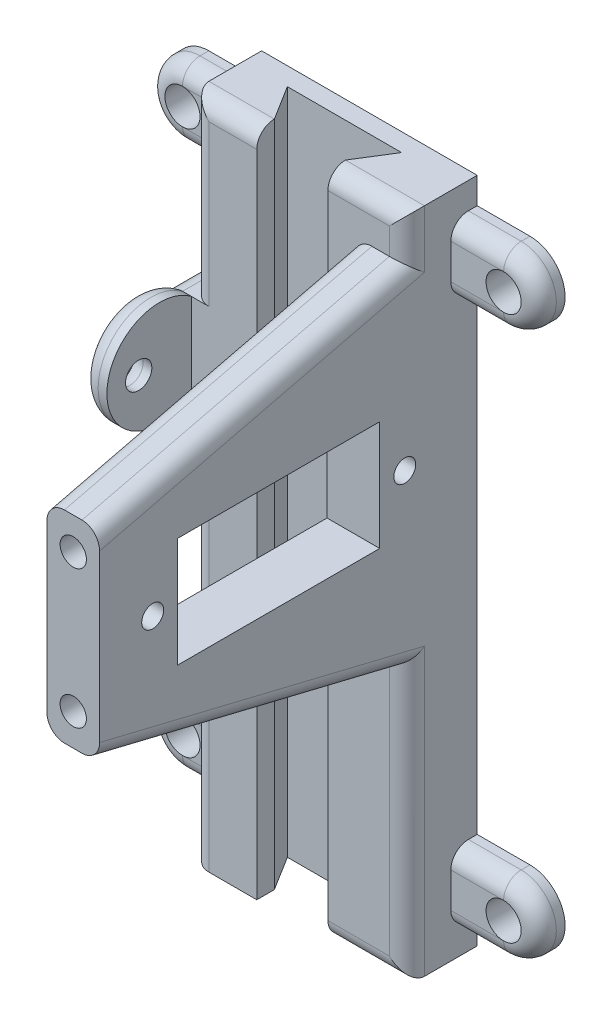
SolidWorks part; units mm, degrees
ref_plane "Front Plane" through (0, 0, 0) normal (0, 0, 1) x (1, 0, 0)
ref_plane "Top Plane" through (0, 0, 0) normal (0, 1, 0) x (1, 0, 0)
ref_plane "Right Plane" through (0, 0, 0) normal (1, 0, 0) x (0, 0, -1)
sketch "Sketch1" plane through (0, 0, 0) normal (0, 0, 1) x (1, 0, 0)
  line L1 (-11.5, 38) -> (11.5, 38)
  line L2 (-11.5, 38) -> (-11.5, -38)
  line L3 (-11.5, -38) -> (11.5, -38)
  line L4 (11.5, 38) -> (11.5, -38)
  line L5 (-11.5, 38) -> (11.5, -38) construction
  line L6 (-11.5, -38) -> (11.5, 38) construction
  point P0 (0, 0)
  dimension "D1" = 76
  dimension "D2" = 23
extrude "Boss-Extrude1" add sketch "Sketch1" along normal blind 8
sketch "Sketch2" plane through (0, -38, 0) normal (0, -1, 0) x (1, 0, 0)
  line L9 (-4.05, 8) -> (4.05, 8)
  line L14 (-11.5, 8) -> (11.5, 8) construction
  line L15 (-4.05, 8) -> (-4.05, 6)
  line L16 (4.05, 8) -> (4.05, 6)
  line L17 (-6.5, 2.065) -> (6.5, 2.065)
  line L18 (-6.5, 2.065) -> (-4.05, 6)
  line L19 (6.5, 2.065) -> (4.05, 6)
  line L20 (0, 2.065) -> (0, 6)
  point P4 (0, 8)
  point P10 (0, 2.065)
  dimension "D1" = 8.1
  dimension "D2" = 2
  dimension "D3" = 2
  dimension "D4" = 13
  dimension "D5" = 4.6354
extrude "Cut-Extrude2" cut sketch "Sketch2" against normal through all both and the other way through all contours L19 L16 L9 L15 L18 L17
sketch "Sketch3" plane through (0, -38, 0) normal (0, -1, 0) x (1, 0, 0)
  line L0 (4.05, 8) -> (13.05, 8)
  line L1 (13.05, 8) -> (13.05, 0)
  line L2 (13.05, 0) -> (11.5, 0)
  line L3 (11.5, 0) -> (11.5, 8)
  line M7 (11.5, 0) -> (11.5, 8)
  dimension "D1" = 9
extrude "Boss-Extrude2" add sketch "Sketch3" against normal blind 76 contours L2 L1 L0 M7 region at (12.275, -38, 4)
sketch "Sketch4" plane through (13.05, 0, 0) normal (1, 0, 0) x (0, 0, -1)
  line L0 (-8, 38) -> (-8, 33)
  line L6 (-8, 38) -> (-8, -38) construction
  line L7 (-8, 33) -> (-43, 24.5)
  line L8 (-43, 24.5) -> (-43, 1.5)
  line L9 (-43, 1.5) -> (-8, -7)
  line L10 (-8, 33) -> (-8, -7)
  point P5 (-43, 13)
  point P10 (-8, 13)
  line M13 (-8, 38) -> (-8, -38)
  dimension "D1" = 5
  dimension "D2" = 23
  dimension "D3" = 35
  dimension "D4" = 40
extrude "Boss-Extrude3" add sketch "Sketch4" against normal blind 6 contours L8 L9 L7 M13 region at (13.05, 13, 23.9259)
sketch "Sketch5" plane through (13.05, 0, 0) normal (1, 0, 0) x (0, 0, -1)
  line L0 (-43, 24.5) -> (-43, 1.5) construction
  line L1 (-34.1, 19.25) -> (-11.1, 19.25)
  line L2 (-34.1, 19.25) -> (-34.1, 6.75)
  line L3 (-34.1, 6.75) -> (-11.1, 6.75)
  line L4 (-11.1, 19.25) -> (-11.1, 6.75)
  line L5 (-34.1, 19.25) -> (-11.1, 6.75) construction
  line L6 (-34.1, 6.75) -> (-11.1, 19.25) construction
  point P0 (-22.6, 13)
  point P7 (-43, 13)
  dimension "D1" = 23
  dimension "D2" = 12.5
  dimension "D3" = 8.9
extrude "Cut-Extrude3" cut sketch "Sketch5" against normal blind 8
sketch "Sketch6" plane through (13.05, 0, 0) normal (1, 0, 0) x (0, 0, -1)
  line L0 (-43, 13) -> (0, 13) construction
  line L1 (-39.8073, 15.003) -> (-34.1, 15.003)
  line L2 (-39.8073, 15.003) -> (-39.8073, 10.997)
  line L3 (-39.8073, 10.997) -> (-34.1, 10.997)
  line L4 (-34.1, 15.003) -> (-34.1, 10.997)
  line L5 (-39.8073, 15.003) -> (-34.1, 10.997) construction
  line L6 (-39.8073, 10.997) -> (-34.1, 15.003) construction
  line L7 (-43, 24.5) -> (-43, 1.5) construction
  line L8 (0, 38) -> (0, -38) construction
  line L9 (-34.1, 19.25) -> (-34.1, 6.75) construction
  line L10 (-22.6, 19.25) -> (-22.6, 6.75) construction
  line L11 (-11.1, 19.25) -> (-34.1, 19.25) construction
  line L12 (-34.1, 6.75) -> (-11.1, 6.75) construction
  line L13 (-11.1, 15.003) -> (-11.1, 10.997)
  line L14 (-5.3927, 15.003) -> (-11.1, 15.003)
  line L15 (-5.3927, 15.003) -> (-5.3927, 10.997)
  line L16 (-5.3927, 10.997) -> (-11.1, 10.997)
  circle A0 centre (-36.9537, 13) radius 1.25
  circle A1 centre (-8.2463, 13) radius 1.25
  point P0 (-36.9537, 13)
  dimension "D2" = 2.5
  dimension "D1" = 0
extrude "Cut-Extrude4" cut sketch "Sketch6" against normal blind 4 contours A0 | A1
sketch "Sketch7" plane through (0, 0, 0) normal (0, 0, -1) x (-1, 0, 0)
  line L0 (-0.775, 38) -> (-0.775, 23.9968) construction
  line L1 (-13.05, 38) -> (11.5, 38) construction
  line L3 (11.5, 31) -> (17.511, 31) construction
  line L4 (11.5, 38) -> (11.5, -38) construction
  line L5 (11.5, 35) -> (17.511, 35)
  line L7 (11.5, 0) -> (-13.05, 0) construction
  line L8 (-13.05, 38) -> (-13.05, -38) construction
  line L9 (-13.05, 31) -> (-19.061, 31) construction
  line L10 (-13.05, 35) -> (-19.061, 35)
  line L11 (-13.05, 27) -> (-19.061, 27)
  line L12 (-13.05, -31) -> (-19.061, -31) construction
  line L13 (-13.05, -35) -> (-19.061, -35)
  line L14 (-13.05, -27) -> (-19.061, -27)
  line L15 (11.5, -31) -> (17.511, -31) construction
  line L16 (11.5, -35) -> (17.511, -35)
  line L17 (11.5, -27) -> (17.511, -27)
  line L18 (11.5, 35) -> (11.5, 27)
  line L19 (-13.05, 35) -> (-13.05, 27)
  line L20 (-13.05, -27) -> (-13.05, -35)
  line L21 (11.5, -27) -> (11.5, -35)
  line L22 (17.511, 27) -> (11.5, 27)
  arc A1 (17.511, 27) -> (17.511, 35) centre (17.511, 31) ccw
  circle A2 centre (17.511, 31) radius 2
  arc A4 (-19.061, 27) -> (-19.061, 35) centre (-19.061, 31) cw
  circle A5 centre (-19.061, 31) radius 2
  circle A6 centre (-19.061, -31) radius 2
  circle A7 centre (17.511, -31) radius 2
  arc A9 (-19.061, -27) -> (-19.061, -35) centre (-19.061, -31) ccw
  arc A11 (17.511, -27) -> (17.511, -35) centre (17.511, -31) cw
  point P10 (11.5, 31)
  point P23 (-13.05, 31)
  point P35 (-13.05, -31)
  point P41 (11.5, -31)
  dimension "D2" = 4
  dimension "D3" = 4
  dimension "D1" = 3
extrude "Boss-Extrude7" add sketch "Sketch7" against normal blind 3
sketch "Sketch8" plane through (-11.5, 0, 0) normal (-1, 0, 0) x (0, 0, 1)
  line L0 (34.1, 13) -> (0, 13) construction
  line L1 (34.1, 19.25) -> (34.1, 6.75) construction
  line L2 (0, 27) -> (0, -27) construction
  line L3 (8, 38) -> (8, -38) construction
  line L4 (8, 33) -> (8, -7) construction
  line L5 (8, 8.2136) -> (8, 17.7864)
  line L6 (0, 17.7864) -> (8, 17.7864)
  line L7 (0, 8.2136) -> (8, 8.2136)
  line L8 (0, 8.2136) -> (0, 17.7864)
  arc A0 (8, 8.2136) -> (8, 17.7864) centre (11.618, 13) ccw
  circle A1 centre (14, 13) radius 1.5
  point P9 (17.618, 13)
  line M8 (8, -38) -> (8, 38)
  line M14 (0, 27) -> (0, -27)
  dimension "D1" = 6
  dimension "D2" = 3
  dimension "D3" = 14
extrude "Boss-Extrude8" add sketch "Sketch8" along normal blind 3 contours L0 L8 L7 M8 | L0 L5 L6 M14 | A0 L0 A1 M8 | L0 A0 L5 A1 region at (-11.5, 10.1813, 12.2425) region at (-11.5, 15.8187, 12.2425) region at (-11.5, 10.6068, 4) region at (-11.5, 15.3932, 4)
sketch "Sketch9" plane through (-11.5, 0, 0) normal (-1, 0, 0) x (0, 0, 1)
sketch "Sketch10" plane through (0, 0, 43) normal (0, 0, 1) x (1, 0, 0)
  line L0 (7.05, 1.5) -> (13.05, 1.5) construction
  line L1 (13.05, 24.5) -> (13.05, 1.5) construction
  line L2 (13.05, 13) -> (-16.8868, 13) construction
  circle A0 centre (10.05, 5.14) radius 1.5
  circle A1 centre (10.05, 20.86) radius 1.5
  dimension "D1" = 3
  dimension "D2" = 3.64
  dimension "D3" = 3
extrude "Cut-Extrude5" cut sketch "Sketch10" against normal blind 4
fillet "Fillet1" radius 2 28 edges at (16.0555, 35, 3) (23.061, 31, 3) (16.0555, -27, 3) (23.061, -31, 3) (-14.5055, -35, 3) (-14.5055, -27, 3) (-14.5055, 27, 3) (-14.5055, 35, 3) (-14.5, 13, 0) (-14.5, 17.7864, 4) (-14.5, 13, 17.618) (-14.5, 8.2136, 4) (-14.5, 11.5, 14) (13.05, 28.75, 25.5) (8.55, 38, 8) (-7.775, 38, 8) (8.55, -38, 8) (13.05, 35.5, 8) (13.05, -22.5, 8) (16.0555, 27, 3) (16.0555, -35, 3) (-21.511, -31, 3) (-21.511, 31, 3) (-11.5, 27.8932, 8) (-11.5, -14.8932, 8) (13.05, -2.75, 25.5) (7.05, 28.75, 25.5) (7.05, -2.75, 25.5)
